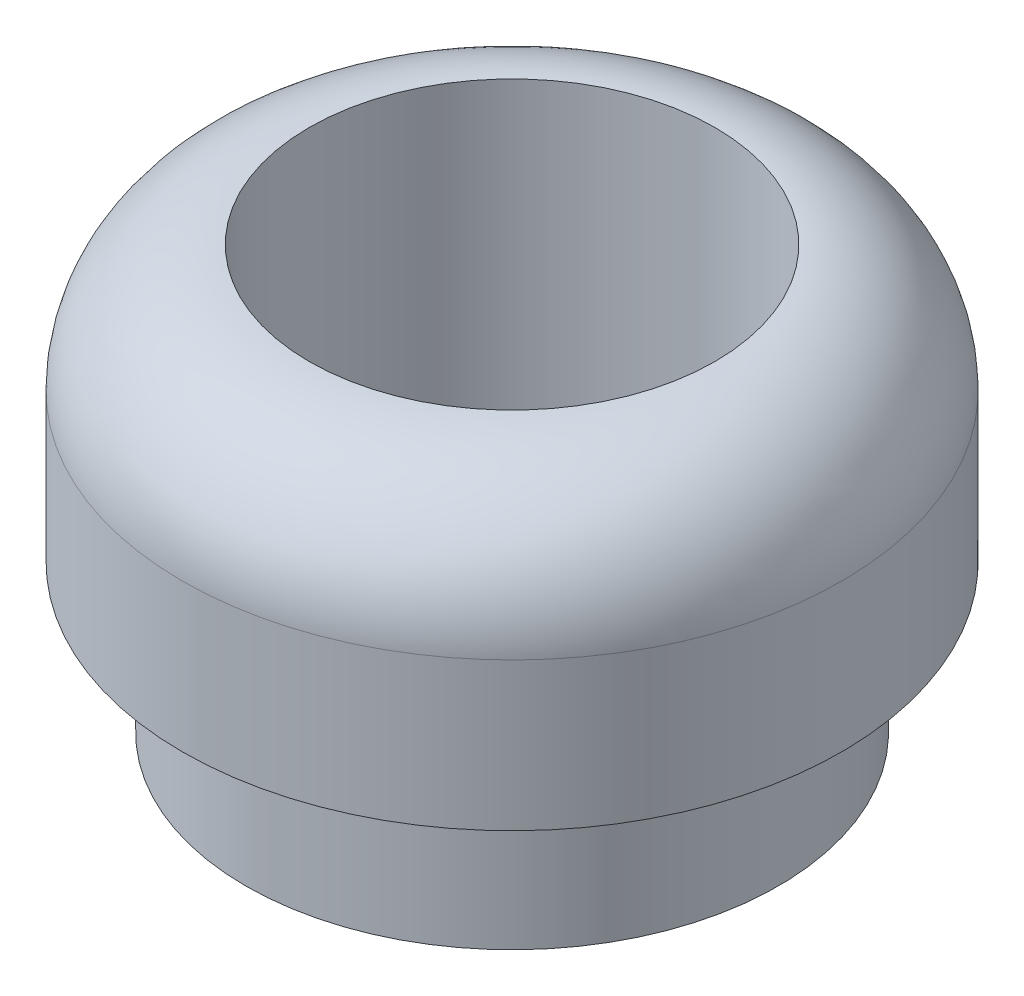
SolidWorks part; units mm, degrees
ref_plane "Front Plane" through (0, 0, 0) normal (0, 0, 1) x (1, 0, 0)
ref_plane "Top Plane" through (0, 0, 0) normal (0, 1, 0) x (1, 0, 0)
ref_plane "Right Plane" through (0, 0, 0) normal (1, 0, 0) x (0, 0, -1)
sketch "Sketch1" plane through (0, 0, 0) normal (0, 1, 0) x (1, 0, 0)
  circle A0 centre (0, 0) radius 4.8 construction
  circle A1 centre (0, 0) radius 7.8
  dimension "D1" = 9.6
  dimension "D2" = 15.6
extrude "Boss-Extrude1" add sketch "Sketch1" along normal blind 10 contours A1
sketch "Sketch2" plane through (0, 10, 0) normal (0, 1, 0) x (1, 0, 0)
  circle A0 centre (0, 0) radius 4.8
  dimension "D1" = 9.6
extrude "Cut-Extrude1" cut sketch "Sketch2" against normal offset from surface (8 mm away) 2 up to face at (0, 0, 7.8)
sketch "Sketch3" plane through (0, 2, 0) normal (0, 1, 0) x (1, 0, 0)
  circle A1 centre (0, 0) radius 7.8 construction
  circle A2 centre (0, 0) radius 2.8
  circle A3 centre (0, 0) radius 2.8
  circle A4 centre (0, 0) radius 7.8
  circle A5 centre (0, 0) radius 6.3
  dimension "D2" = 3.5
  dimension "D1" = 2
extrude "Cut-Extrude2" cut sketch "Sketch3" against normal through all and the other way blind 1.5 contours A4 A5 | A3 region at (0, 2, 0) region at (-7.5794, 2, 0)
fillet "Fillet1" radius 3 1 edges at (0, 10, 7.8) type face fillet first side face at (0, 10, 4.8) second side face at (0, 3.5, 7.8)
